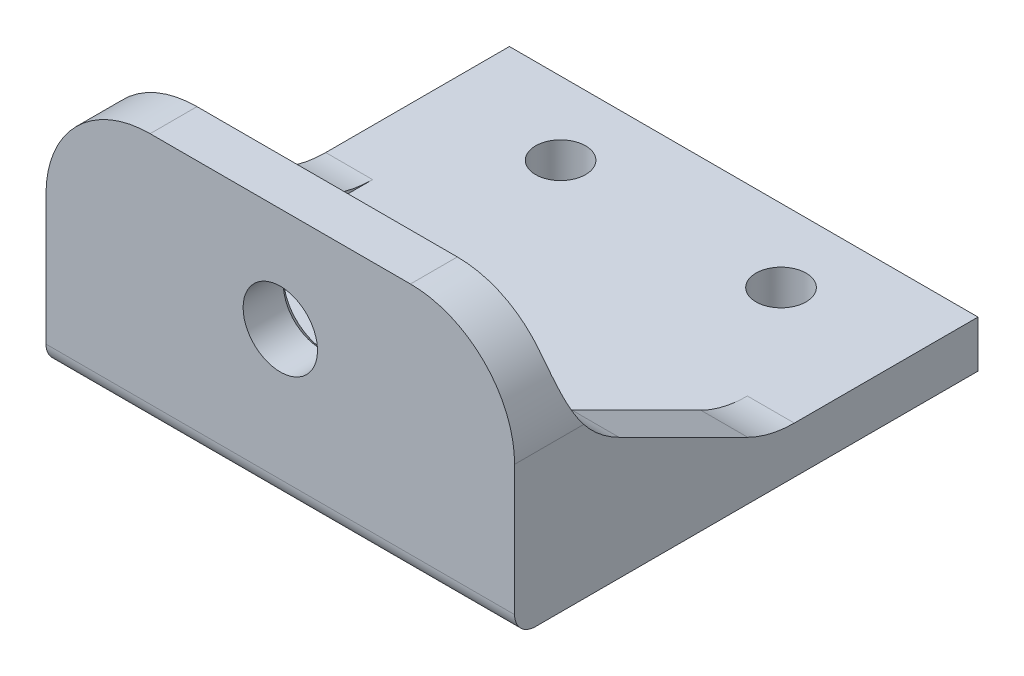
SolidWorks part; units mm, degrees
material "ABS PC"
ref_plane "Front Plane" through (0, 0, 0) normal (0, 0, 1) x (1, 0, 0)
ref_plane "Top Plane" through (0, 0, 0) normal (0, 1, 0) x (1, 0, 0)
ref_plane "Right Plane" through (0, 0, 0) normal (1, 0, 0) x (0, 0, -1)
sketch "Sketch1" plane through (0, 0, 0) normal (0, 1, 0) x (1, 0, 0)
  line L5 (-22.5, -77.5) -> (22.5, -77.5)
  line L6 (-22.5, -77.5) -> (-22.5, 0)
  line L8 (22.5, -77.5) -> (22.5, 0)
  line L9 (-22.5, -77.5) -> (22.5, 0) construction
  line L10 (-22.5, 0) -> (22.5, -77.5) construction
  arc A0 (22.5, 0) -> (-22.5, 0) centre (0, 0) ccw
  point P2 (0, -38.75)
  dimension "D1" = 45
  dimension "D2" = 100
  dimension "D3" = 45
extrude "Boss-Extrude1" add sketch "Sketch1" along normal blind 4.5
sketch "Sketch2" plane through (0, 4.5, 0) normal (0, 1, 0) x (1, 0, 0)
  line L0 (-6.697, 16.1679) -> (6.697, 16.1679) construction
  circle A0 centre (0, 0) radius 17.5 construction
  circle A1 centre (0, 0) radius 17.5 construction
  circle A2 centre (0, 0) radius 17.5 construction
  circle A3 centre (0, 0) radius 17.5 construction
  circle A4 centre (0, 0) radius 17.5 construction
  circle A5 centre (0, 0) radius 17.5 construction
  circle A6 centre (0, 0) radius 17.5 construction
  circle A7 centre (0, 0) radius 17.5 construction
  point P3 (-6.697, 16.1679)
  point P5 (-16.1679, -6.697)
  point P7 (6.697, 16.1679)
  point P9 (16.1679, 6.697)
  point P11 (16.1679, -6.697)
  point P13 (6.697, -16.1679)
  point P15 (-6.697, -16.1679)
  point P16 (0, 0)
  point P18 (-16.1679, 6.697)
  dimension "D1" = 35
  dimension "D2" = 8
hole_wizard "M5 Clearance Hole1" positions "Sketch3" profile "Sketch4" hole size "M5" standard "ANSI Metric" end condition through all
sketch "Sketch3" plane through (0, 4.5, 0) normal (0, 1, 0) x (1, 0, 0)
  point P0 (-6.697, -16.1679)
  point P3 (6.697, -16.1679)
  point P6 (6.697, 16.1679)
  point P15 (-6.697, 16.1679)
sketch "Sketch4" plane through (-6.697, 4.5, 16.1679) normal (1, 0, 0) x (0, 0, 1)
  line L0 (0, 0) -> (0, 4.5)
  line L1 (0, 4.5) -> (2.75, 4.5)
  line L2 (2.75, 4.5) -> (2.75, 0.025)
  line L3 (2.75, 0.025) -> (2.775, 0)
  line L5 (2.775, 0) -> (0, 0)
  line L6 (-2.75, 0.025) -> (-2.775, 0) construction
  line L11 (0, -6.35) -> (0, 107.95) construction
  dimension "Thru Hole Dia." = 5.5
  dimension "Thru Hole Depth" = 4.5
  dimension "Near C'Sink Dia." = 5.55
  dimension "Near C'Sink Angle" = 90
sketch "Sketch5" plane through (0, 4.5, 0) normal (0, 1, 0) x (1, 0, 0)
  circle A0 centre (0, 0) radius 12.5
  dimension "D1" = 25
extrude "Cut-Extrude1" cut sketch "Sketch5" against normal through all
sketch "Sketch6" [suppressed] plane through (0, 6.35, 0) normal (0, 1, 0) x (1, 0, 0)
  line L0 (-22.5, -77.5) -> (22.5, -77.5) construction
  circle A0 centre (0, -71) radius 3.3782
  dimension "D1" = 6.7564
  dimension "D2" = 6.5
sketch "Sketch7" [suppressed] plane through (0, 6.35, 0) normal (0, 1, 0) x (1, 0, 0)
  line L0 (12.5, -58.5) -> (-12.5, -58.5) construction
  line L1 (12.5, -63) -> (-12.5, -63)
  line L2 (12.5, -54) -> (-12.5, -54)
  line L3 (0, -71) -> (0, 0) construction
  line L4 (12.5, -42.5) -> (-12.5, -42.5) construction
  line L5 (12.5, -47) -> (-12.5, -47)
  line L6 (12.5, -38) -> (-12.5, -38)
  line L7 (12.5, -26.5) -> (-12.5, -26.5) construction
  line L8 (12.5, -31) -> (-12.5, -31)
  line L9 (12.5, -22) -> (-12.5, -22)
  arc A0 (12.5, -63) -> (12.5, -54) centre (12.5, -58.5) ccw
  arc A1 (-12.5, -54) -> (-12.5, -63) centre (-12.5, -58.5) ccw
  arc A2 (12.5, -47) -> (12.5, -38) centre (12.5, -42.5) ccw
  arc A3 (-12.5, -38) -> (-12.5, -47) centre (-12.5, -42.5) ccw
  arc A4 (12.5, -31) -> (12.5, -22) centre (12.5, -26.5) ccw
  arc A5 (-12.5, -22) -> (-12.5, -31) centre (-12.5, -26.5) ccw
  circle A6 centre (0, -71) radius 3.3782 construction
  point P2 (0, -58.5)
  point P15 (0, -42.5)
  point P22 (0, -26.5)
  point P28 (0, -63)
  dimension "D2" = 4.5
  dimension "D4" = 8
  dimension "D3" = 25
  dimension "D1" = 3
extrude "Cut-Extrude3" [suppressed] cut sketch "Sketch7" against normal through all
sketch "Sketch12" plane through (0, 0, 77.5) normal (0, 0, 1) x (1, 0, 0)
  line L0 (-22.5, 4.5) -> (22.5, 4.5) construction
  line L1 (22.5, 0) -> (-22.5, 0)
  line L2 (22.5, 0) -> (22.5, 24.5)
  line L3 (22.5, 24.5) -> (-22.5, 24.5)
  line L4 (-22.5, 0) -> (-22.5, 24.5)
  dimension "D1" = 20
extrude "Boss-Extrude2" add sketch "Sketch12" along normal blind 4.5
sketch "Sketch13" plane through (0, 0, 77.5) normal (0, 0, -1) x (-1, 0, 0)
  line L0 (22.5, 4.5) -> (-22.5, 4.5) construction
  point P0 (0, 14.5)
  dimension "D1" = 10
hole_wizard "1/4 Clearance Hole1" positions "Sketch16" profile "Sketch17" hole size "1/4" standard "ANSI Inch" end condition through all
sketch "Sketch16" plane through (0, 0, 77.5) normal (0, 0, -1) x (-1, 0, 0)
  point P0 (0, 14.5)
sketch "Sketch17" plane through (0, 14.5, 77.5) normal (1, 0, 0) x (0, 1, 0)
  line L0 (0, 0) -> (0, 4.5)
  line L1 (0, 4.5) -> (3.5712, 4.5)
  line L2 (3.5712, 4.5) -> (3.5712, 0.635)
  line L3 (3.5712, 0.635) -> (4.2062, 0)
  line L5 (4.2062, 0) -> (0, 0)
  line L6 (-3.5712, 0.635) -> (-4.2062, 0) construction
  line L11 (0, -6.35) -> (0, 107.95) construction
  dimension "Thru Hole Dia." = 7.1425
  dimension "Thru Hole Depth" = 4.5
  dimension "Near C'Sink Dia." = 8.4125
  dimension "Near C'Sink Angle" = 90
fillet "Fillet1" radius 10 2 edges at (-22.5, 24.5, 79.75) (22.5, 24.5, 79.75)
fillet "Fillet2" radius 2 2 edges at (0, 0, 82) (0, 4.5, 77.5)
ref_plane "Plane1" through (0, 0, -22.5) normal (0, 0, 1) x (1, 0, 0)
sketch "Sketch18" plane through (0, 0, -22.5) normal (0, 0, 1) x (1, 0, 0)
  line L1 (-32.4973, -4.485) -> (73.8257, -4.485)
  line L2 (-32.4973, -4.485) -> (-32.4973, 66.5178)
  line L3 (-32.4973, 66.5178) -> (73.8257, 66.5178)
  line L4 (73.8257, -4.485) -> (73.8257, 66.5178)
extrude "Cut-Extrude4" cut sketch "Sketch18" along normal blind 60
sketch "Sketch19" plane through (0, 0, 0) normal (0, -1, 0) x (1, 0, 0)
  line L0 (-10.5848, 44.5) -> (10.5848, 44.5) construction
  line L1 (22.5, 37.5) -> (-22.5, 37.5) construction
  point P2 (0, 44.5)
  point P5 (0, 37.5)
  dimension "D1" = 7
  dimension "D2" = 21.1696
hole_wizard "M4 Clearance Hole1" positions "Sketch20" profile "Sketch21" hole size "M4" standard "ANSI Metric" end condition through all
sketch "Sketch20" plane through (0, 0, 0) normal (0, -1, 0) x (-1, 0, 0)
  point P0 (10.5848, -44.5)
  point P3 (-10.5848, -44.5)
sketch "Sketch21" plane through (-10.5848, 0, 44.5) normal (1, 0, 0) x (0, 0, -1)
  line L0 (0, 0) -> (0, 24.5)
  line L1 (0, 24.5) -> (2.4, 24.5)
  line L2 (2.4, 24.5) -> (2.4, 0)
  line L5 (2.4, 0) -> (0, 0)
  line L11 (0, -6.35) -> (0, 107.95) construction
  dimension "Thru Hole Dia." = 4.8
  dimension "Thru Hole Depth" = 24.5
sketch "Sketch23" plane through (-22.5, 0, 0) normal (-1, 0, 0) x (0, 0, 1)
  line L0 (77.5, 14.5) -> (57.5, 4.5)
  line L1 (77.5, 14.5) -> (77.5, 6.5) construction
  line L2 (37.5, 4.5) -> (75.5, 4.5) construction
  line L3 (57.5, 4.5) -> (77.5, 4.5)
  line L4 (77.5, 4.5) -> (77.5, 14.5)
  dimension "D1" = 10
  dimension "D2" = 20
extrude "Boss-Extrude3" add sketch "Sketch23" against normal blind 4.5
fillet "Fillet3" radius 10 2 edges at (-20.25, 4.5, 57.5) (-20.25, 14.5, 77.5)
mirror "Mirror1" about plane through (0, 0, 0) normal (1, 0, 0) of "Boss-Extrude3", "Fillet3"
